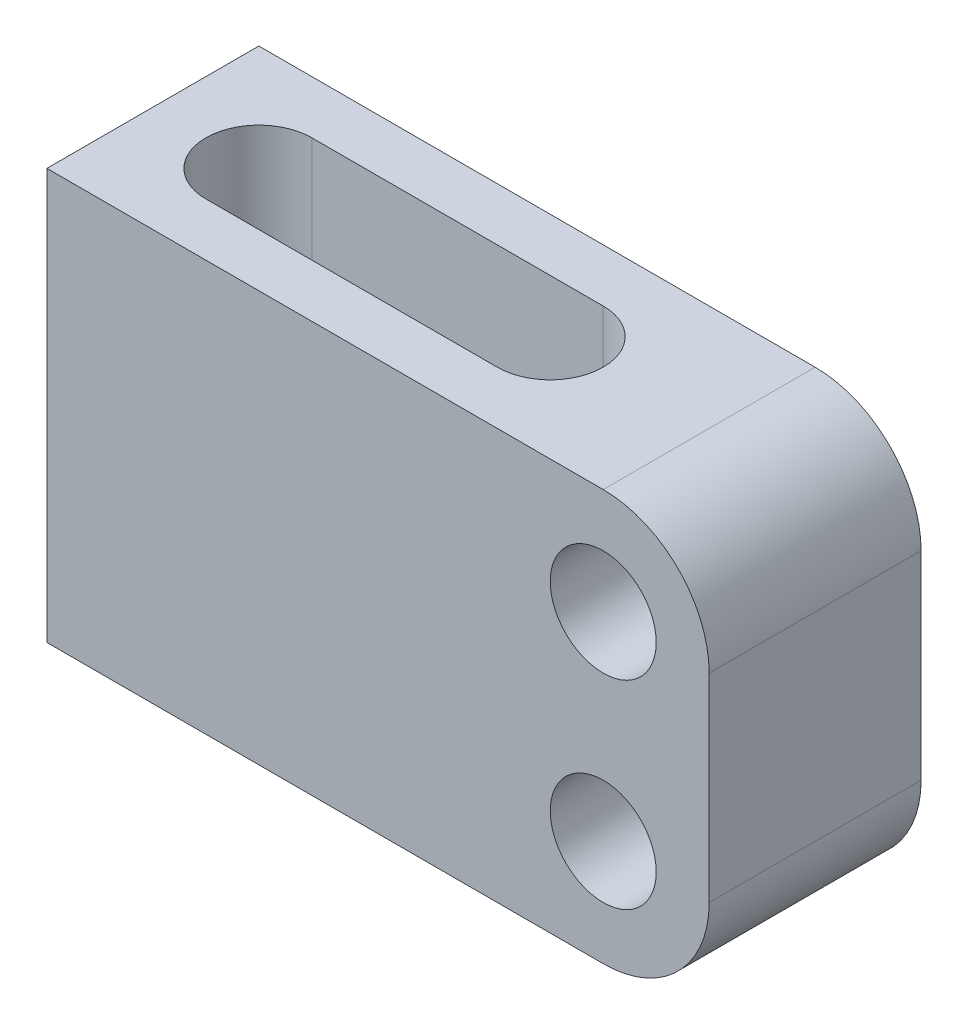
SolidWorks part; units mm, degrees
material "ABS"
ref_plane "Front Plane" through (0, 0, 0) normal (0, 0, 1) x (1, 0, 0)
ref_plane "Top Plane" through (0, 0, 0) normal (0, 1, 0) x (1, 0, 0)
ref_plane "Right Plane" through (0, 0, 0) normal (1, 0, 0) x (0, 0, -1)
sketch "Sketch1" plane through (0, 0, 0) normal (0, 0, 1) x (1, 0, 0)
  line L0 (0, 24.6616) -> (0, -42.6931) construction
  line L1 (8, 0) -> (8, -15)
  line L2 (0, 8) -> (-42, 8)
  line L3 (-42, 8) -> (-42, -23)
  line L4 (-42, -23) -> (0, -23)
  circle A0 centre (0, 0) radius 4
  circle A1 centre (0, -15) radius 4
  arc A2 (8, -15) -> (0, -23) centre (0, -15) cw
  arc A3 (8, 0) -> (0, 8) centre (0, 0) ccw
  dimension "D1" = 8
  dimension "D2" = 8
  dimension "D4" = 8
  dimension "D3" = 15
  dimension "D5" = 50
extrude "Boss-Extrude1" add sketch "Sketch1" against normal blind 16
sketch "Sketch2" plane through (0, 8, 0) normal (0, 1, 0) x (1, 0, 0)
  line L0 (-42, 8) -> (8, 8) construction
  line L1 (-42, 16) -> (-42, 0) construction
  line L2 (8, 16) -> (8, 0) construction
  line L3 (-34, 12) -> (-12, 12)
  line L4 (-34, 4) -> (-12, 4)
  arc A0 (-34, 12) -> (-34, 4) centre (-34, 8) ccw
  arc A1 (-12, 4) -> (-12, 12) centre (-12, 8) ccw
  dimension "D1" = 8
  dimension "D3" = 8
  dimension "D2" = 8
  dimension "D4" = 20
extrude "Cut-Extrude1" cut sketch "Sketch2" against normal through all
equation "\"rod_diameter\"= 8"
equation "\"rod_hole_thickness\"= 4"
equation "\"rod_radius\"= \"rod_diameter\" / 2"
equation "\"platter_diameter\"= 320"
equation "\"platter_radius\"= \"platter_diameter\" / 2"
equation "\"extruder_mount_hole_spacing\"= 75"
equation "\"arm_rod_spacing\"= 40"
equation "\"top_frame_rod_spacing\"= \"arm_rod_spacing\" + 40"
equation "\"motor_level_rod_spacing\"= 15"
equation "\"linear_bearing_diameter\"= 15"
equation "\"z_rod_spacing\"= 75"
equation "\"platter_rod_spacing\"= 50"
equation "\"rod_nut_thickness\"= 6.5"
equation "\"rod_nut_inscribed_diameter\"= 13"
equation "\"z_height\"= 400"
equation "\"D1@Sketch1\"=\"rod_diameter\""
equation "\"D2@Sketch1\"=\"rod_diameter\""
equation "\"D3@Sketch1\"=\"motor_level_rod_spacing\""
equation "\"D4@Sketch1\"=\"rod_radius\"+\"rod_hole_thickness\""
equation "\"D1@Boss-Extrude1\"= \"rod_diameter\" + \"rod_hole_thickness\" * 2"
equation "\"D1@Sketch2\"=\"rod_diameter\""
equation "\"D2@Sketch2\"=\"rod_radius\"+\"rod_hole_thickness\""
equation "\"D3@Sketch2\"=\"rod_diameter\""
equation "\"D4@Sketch2\"=\"rod_diameter\"+\"rod_hole_thickness\"*2 +\"rod_radius\""
